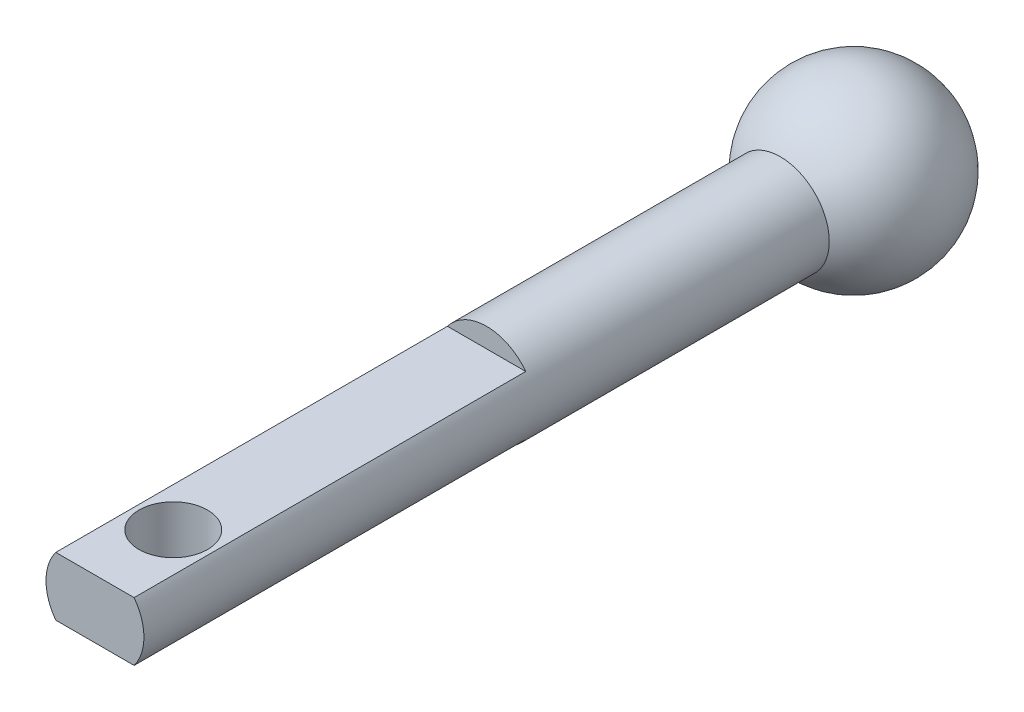
SolidWorks part; units mm, degrees
ref_plane "Front Plane" through (0, 0, 0) normal (0, 0, 1) x (1, 0, 0)
ref_plane "Top Plane" through (0, 0, 0) normal (0, 1, 0) x (1, 0, 0)
ref_plane "Right Plane" through (0, 0, 0) normal (1, 0, 0) x (0, 0, -1)
sketch "Sketch1" plane through (0, 0, 0) normal (0, 1, 0) x (1, 0, 0)
  line L0 (0, 43.2417) -> (0, 0)
  line L10 (0, 0) -> (2.5, 0)
  line L11 (2.5, 35) -> (2.5, 0)
  arc A0 (2.5, 35) -> (0, 43.2417) centre (0, 38.7417) ccw
  dimension "D1" = 4.5
  dimension "D2" = 35
  dimension "D3" = 2.5
revolve "Revolve1" add sketch "Sketch1" angle 360 about L0
sketch "Sketch2" plane through (0, 0, 0) normal (0, 0, 1) x (1, 0, 0)
  line L0 (-2, 1.5) -> (2, 1.5)
  line L5 (-2, -1.5) -> (2, -1.5)
  line L6 (5.0514, 0) -> (-4.2554, 0) construction
  line L7 (-5.635, 2.5) -> (4.7759, 2.5) construction
  circle A5 centre (0, 0) radius 2.5 construction
  circle A6 centre (0, 0) radius 2.5
  circle A7 centre (0, 0) radius 2.5 construction
  circle M12 centre (0, 0) radius 2.5
  dimension "D1" = 1
extrude "Cut-Extrude3" cut sketch "Sketch2" against normal blind 20 contours L0 M12 | L5 M12 region at (0, 1.9078, 0) region at (0, -1.9078, 0)
sketch "Sketch4" plane through (0, 0, 0) normal (0, 1, 0) x (1, 0, 0)
  circle A0 centre (0, 4) radius 1.75
  dimension "D1" = 3.5
  dimension "D2" = 4
extrude "Cut-Extrude4" cut sketch "Sketch4" against normal through all both and the other way through all
